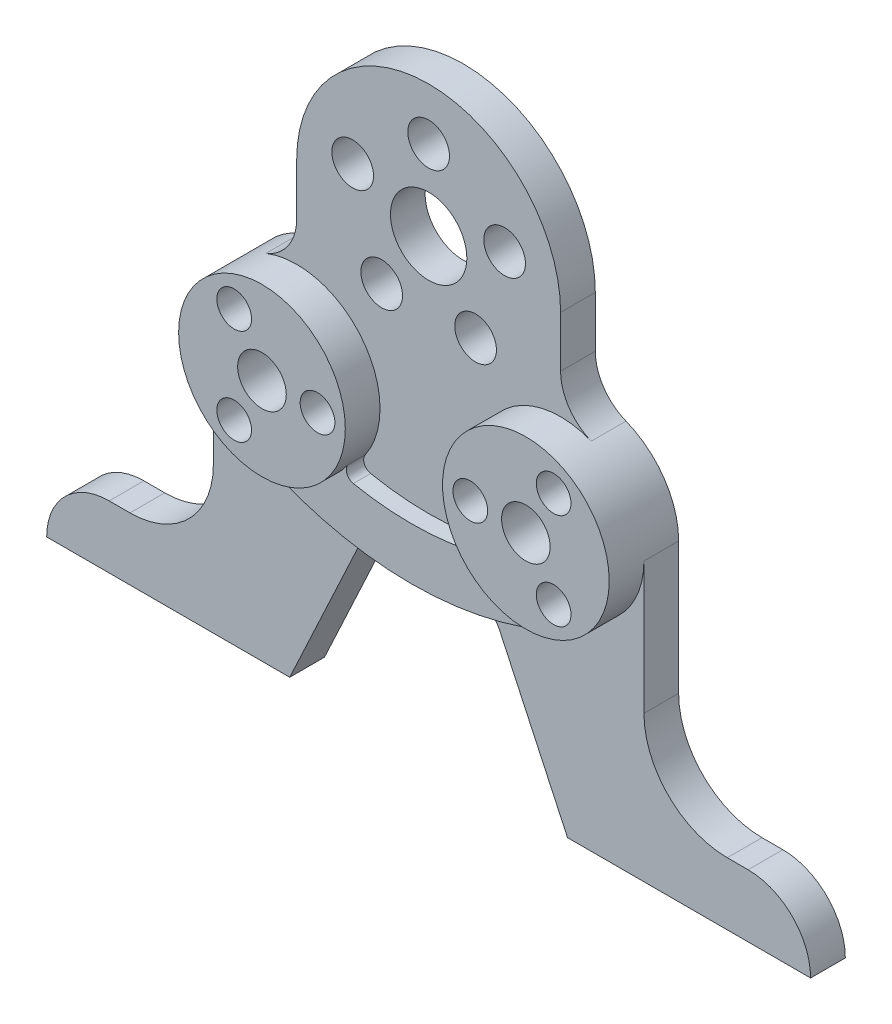
SolidWorks part; units mm, degrees
ref_plane "Спереди" through (0, 0, 0) normal (0, 0, 1) x (1, 0, 0)
ref_plane "Сверху" through (0, 0, 0) normal (0, 1, 0) x (1, 0, 0)
ref_plane "Справа" through (0, 0, 0) normal (1, 0, 0) x (0, 0, -1)
sketch "Эскиз1" plane through (0, 0, 0) normal (0, 0, 1) x (1, 0, 0)
  line L0 (0, 71.1375) -> (0, -69.5845) construction
  line L1 (-38, 50) -> (-38, -69.3523) construction
  line L2 (38, 50) -> (38, -56.4624) construction
  line L3 (0, 0) -> (-38, 0) construction
  line L4 (-38, 50) -> (-38, 35.327)
  line L5 (-110, -80) -> (-40, -80)
  line L6 (-62, 0) -> (-62, -145.1531) construction
  line L7 (38, -80) -> (185.2299, -80) construction
  line L8 (-62, 0) -> (-62, -38)
  line L9 (-40, -80) -> (-20.4132, -37.996)
  line L10 (62, 0) -> (62, -38)
  line L11 (38, 50) -> (38, 35.327)
  line L13 (-38, 50) -> (-38, 35.327)
  line L14 (-62, 0) -> (-62, -38)
  line L15 (40, -80) -> (20.4132, -37.996)
  line L16 (62, 0) -> (62, -38)
  line L17 (38, 50) -> (38, 35.327)
  line L18 (40, -80) -> (110, -80)
  line L19 (86, -62) -> (92, -62)
  line L20 (-92, -62) -> (-86, -62)
  line L21 (-1040, -80) -> (-38, -80) construction
  circle A0 centre (0, 50) radius 11
  arc A1 (38, 50) -> (-38, 50) centre (0, 50) ccw
  circle A2 centre (0, 73) radius 6
  circle A3 centre (21.8743, 57.1074) radius 6
  circle A4 centre (13.5191, 31.3926) radius 6
  circle A5 centre (-13.5191, 31.3926) radius 6
  circle A6 centre (-21.8743, 57.1074) radius 6
  circle A7 centre (-38, 0) radius 24
  circle A8 centre (-38, 0) radius 7
  circle A9 centre (-22, 0) radius 5
  circle A10 centre (-46, -13.8564) radius 5
  circle A11 centre (-46, 13.8564) radius 5
  arc A12 (-46.8421, 22.3118) -> (-38, 35.327) centre (-52, 35.327) ccw
  arc A13 (-92, -62) -> (-110, -80) centre (-92, -80) ccw
  arc A14 (-86, -62) -> (-62, -38) centre (-86, -38) ccw
  arc A15 (86, -62) -> (62, -38) centre (86, -38) cw
  arc A16 (92, -62) -> (110, -80) centre (92, -80) cw
  arc A17 (46.8421, 22.3118) -> (38, 35.327) centre (52, 35.327) cw
  circle A18 centre (46, 13.8564) radius 5
  circle A19 centre (46, -13.8564) radius 5
  circle A20 centre (22, 0) radius 5
  circle A21 centre (38, 0) radius 7
  circle A22 centre (38, 0) radius 24
  circle A23 centre (21.8743, 57.1074) radius 6
  circle A24 centre (13.5191, 31.3926) radius 6
  circle A25 centre (-13.5191, 31.3926) radius 6
  circle A26 centre (-21.8743, 57.1074) radius 6
  arc A27 (-50, -20.7846) -> (50, -20.7846) centre (0, 65.8179) ccw
  arc A28 (-12.1877, -33.4366) -> (-20.4132, -37.996) centre (-13.1628, -41.3769) ccw
  arc A29 (-16.6966, -17.5261) -> (16.6966, -17.5261) centre (0, 65.8179) ccw
  arc A30 (-18.2616, -13.6526) -> (-16.6966, -17.5261) centre (-16.2055, -15.0748) ccw
  arc A31 (18.2616, -13.6526) -> (16.6966, -17.5261) centre (16.2055, -15.0748) cw
  arc A32 (16.6966, -17.5261) -> (-16.6966, -17.5261) centre (0, 65.8179) cw
  arc A33 (12.1877, -33.4366) -> (20.4132, -37.996) centre (13.1628, -41.3769) cw
  circle A34 centre (21.8743, 57.1074) radius 6
  circle A35 centre (13.5191, 31.3926) radius 6
  circle A36 centre (-13.5191, 31.3926) radius 6
  circle A37 centre (-21.8743, 57.1074) radius 6
  circle A38 centre (-38, 0) radius 24
  circle A39 centre (-38, 0) radius 7
  circle A40 centre (-22, 0) radius 5
  circle A41 centre (-46, -13.8564) radius 5
  circle A42 centre (-46, 13.8564) radius 5
  arc A43 (-46.8421, 22.3118) -> (-38, 35.327) centre (-52, 35.327) ccw
  arc A44 (-92, -62) -> (-110, -80) centre (-92, -80) ccw
  arc A45 (-86, -62) -> (-62, -38) centre (-86, -38) ccw
  arc A46 (86, -62) -> (62, -38) centre (86, -38) cw
  arc A47 (92, -62) -> (110, -80) centre (92, -80) cw
  arc A48 (46.8421, 22.3118) -> (38, 35.327) centre (52, 35.327) cw
  circle A49 centre (46, 13.8564) radius 5
  circle A50 centre (46, -13.8564) radius 5
  circle A51 centre (22, 0) radius 5
  circle A52 centre (38, 0) radius 7
  circle A53 centre (38, 0) radius 24
  circle A54 centre (21.8743, 57.1074) radius 6
  circle A55 centre (13.5191, 31.3926) radius 6
  circle A56 centre (-13.5191, 31.3926) radius 6
  circle A57 centre (-21.8743, 57.1074) radius 6
  point P19 (0, 50)
  point P36 (-38, 0)
  dimension "D1" = 22
  dimension "D2" = 50
  dimension "D3" = 76
  dimension "D4" = 12
  dimension "D7" = 48
  dimension "D8" = 14
  dimension "D9" = 10
  dimension "D12" = 28
  dimension "D15" = 18
  dimension "D16" = 48
  dimension "D17" = 200
  dimension "D20" = 16
  dimension "D21" = 85
  dimension "D22" = 5
  dimension "D5" = 23
  dimension "D10" = 16
  dimension "D13" = 130
  dimension "D14" = 110
  dimension "D18" = 80
  dimension "D19" = 65
  dimension "D6" = 5
  dimension "D11" = 3
extrude "Бобышка-Вытянуть1" add sketch "Эскиз1" along normal blind 10 contours A27 A33 L15 L18 A16 L19 A15 L10 A22 | A28 A27 A7 L8 A14 L20 A13 L5 L9 | A31 A22 A17 L11 A1 L4 A12 A7 A30 A29 A6 A5 A4 A3 A2 A0 region at (0, 37.8136, 0) region at (-57.3562, -55.0327, 0) region at (57.3562, -55.0327, 0)
extrude "Бобышка-Вытянуть2" add sketch "Эскиз1<3>" along normal blind 15 contours A22 A31 A29 A30 A7 A27 region at (0, -25.6802, 0)
sketch "Эскиз1<3>" plane through (0, 0, 0) normal (0, 0, 1) x (1, 0, 0) same geometry as "Эскиз1"
extrude "Бобышка-Вытянуть3" add sketch "Эскиз1<4>" along normal blind 20 contours A7 A11 A10 A9 A8 | A22 A20 A18 A19 A21 region at (-24.8946, 19.2906, 0) region at (57.2906, 13.1054, 0)
sketch "Эскиз1<4>" plane through (0, 0, 0) normal (0, 0, 1) x (1, 0, 0) same geometry as "Эскиз1"
